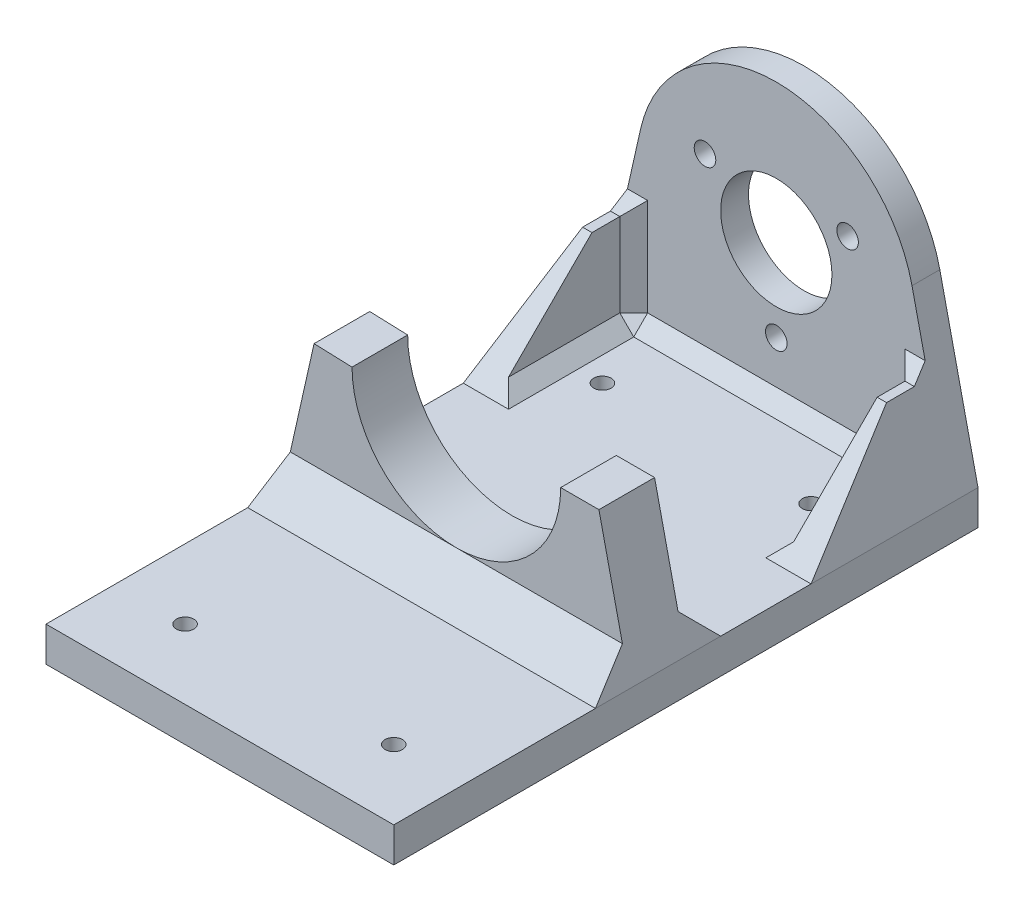
SolidWorks part; units mm, degrees
ref_plane "Plan de face" through (0, 0, 0) normal (0, 0, 1) x (1, 0, 0)
ref_plane "Plan de dessus" through (0, 0, 0) normal (0, 1, 0) x (1, 0, 0)
ref_plane "Plan de droite" through (0, 0, 0) normal (1, 0, 0) x (0, 0, -1)
sketch "Esquisse1" plane through (0, 0, 0) normal (0, 0, 1) x (1, 0, 0)
  line L0 (-25, -20) -> (-25, -25)
  line L1 (0, 0) -> (0, -30) construction
  line L2 (-25, -20) -> (-19.5122, 4.3902)
  line L3 (25, -20) -> (19.5122, 4.3902)
  line L4 (-25, -25) -> (25, -25)
  line L5 (25, -25) -> (25, -20)
  line L6 (0, -11.8357) -> (10.25, 5.9178) construction
  line L7 (10.25, 5.9178) -> (-10.25, 5.9178) construction
  line L8 (-10.25, 5.9178) -> (0, -11.8357) construction
  circle A0 centre (0, 0) radius 20 construction
  arc A1 (-19.5122, 4.3902) -> (19.5122, 4.3902) centre (0, 0) cw
  circle A2 centre (0, 0) radius 8
  circle A3 centre (0, 0) radius 5.9178 construction
  circle A4 centre (-10.25, 5.9178) radius 1.55
  circle A5 centre (10.25, 5.9178) radius 1.55
  circle A6 centre (0, -11.8357) radius 1.55
  point P20 (0, 0)
  point P24 (0, 0)
  dimension "D1" = 40
  dimension "D5" = 60
  dimension "D6" = 60
  dimension "D8" = 3.1
  dimension "D2" = 50
  dimension "D3" = 5
  dimension "D4" = 25
  dimension "D7" = 20.5
  dimension "D9" = 3
extrude "Boss.-Extru.1" add sketch "Esquisse1" along normal blind 4
sketch "Esquisse2" plane through (0, 0, 4) normal (0, 0, 1) x (1, 0, 0)
  line L0 (25, -25) -> (25, -20) construction
  line L1 (-25, -25) -> (25, -25)
  line L2 (-25, -25) -> (-25, -20)
  line L3 (-25, -20) -> (25, -20)
  line L4 (25, -25) -> (25, -20)
extrude "Boss.-Extru.2" add sketch "Esquisse2" along normal blind 80
sketch "Esquisse4" plane through (0, 0, 4) normal (0, 0, 1) x (1, 0, 0)
  line L0 (-20.5, 0) -> (-20.5, -20)
  line L1 (-19.5122, 4.3902) -> (-25, -20) construction
  line L2 (25, -20) -> (-25, -20) construction
  line L3 (-20.5, -20) -> (-25, -20)
  line L4 (-25, -20) -> (-25, -25) construction
  line L5 (-25, -20) -> (-20.5, 0)
  line L6 (0, 0) -> (0, -20) construction
  line L7 (25, -20) -> (-25, -20) construction
  line L8 (20.5, -20) -> (25, -20)
  line L9 (25, -20) -> (20.5, 0)
  line L10 (20.5, 0) -> (20.5, -20)
extrude "Boss.-Extru.3" add sketch "Esquisse4" along normal blind 20
sketch "Esquisse5" plane through (-20.5, 0, 0) normal (1, 0, 0) x (0, 0, -1)
  line L0 (-24, -20) -> (-4, 0) construction
  line L1 (-4, 0) -> (-24, 0)
  line L2 (-24, 0) -> (-24, -20)
  line L3 (-4, 0) -> (-4, -6)
  line L4 (-4, 0) -> (-4, 4.3902) construction
  line L5 (-4, -6) -> (-10, -6)
  line L6 (-10, -6) -> (-24, -20)
extrude "Enlèv. mat.-Extru.2" cut sketch "Esquisse5" against normal through all and the other way through all
chamfer "Chanfrein1" distance 2 angle 45 5 edges at (-20.5, -13, 4) (-20.5, -20, 14) (20.5, -13, 4) (20.5, -20, 14) (0, -20, 4)
chamfer "Chanfrein2" distance 2 angle 45 2 edges at (20.175, -6, 4) (-20.175, -6, 4)
ref_plane "Plan1" through (0, 0, 46) normal (0, 0, 1) x (1, 0, 0)
sketch "Esquisse7" plane through (0, 0, 46) normal (0, 0, 1) x (1, 0, 0)
  line L0 (-15, 0) -> (-20.4561, 0.1951)
  line L1 (-19.5122, 4.3902) -> (-21.4, -4) construction
  line L2 (-20.4561, 0.1951) -> (-25, -20)
  line L3 (-25, -20) -> (25, -20)
  line L4 (25, -20) -> (20.5, 0)
  line L5 (21.4, -4) -> (19.5122, 4.3902) construction
  line L6 (20.5, 0) -> (15, 0)
  arc A0 (-15, 0) -> (15, 0) centre (0, 0) ccw
  point P0 (0, 0)
extrude "Boss.-Extru.4" add sketch "Esquisse7" along normal blind 4 and the other way blind 4
chamfer "Chanfrein3" distance 5 angle 45 2 edges at (0, -20, 42) (0, -20, 50)
sketch "Esquisse6" plane through (0, -20, 0) normal (0, 1, 0) x (1, 0, 0)
  line L0 (0, 0) -> (0, -84) construction
  line L1 (25, -84) -> (-25, -84) construction
  line L2 (-25, -44) -> (25, -44) construction
  line L3 (-25, -84) -> (-25, -55) construction
  line L4 (25, -84) -> (25, -55) construction
  circle A0 centre (-15, -74) radius 1.25
  circle A1 centre (15, -74) radius 1.25
  circle A2 centre (15, -14) radius 1.25
  circle A3 centre (-15, -14) radius 1.25
  circle A4 centre (-15, -44) radius 1.25
  circle A5 centre (15, -44) radius 1.25
  dimension "D2" = 10
  dimension "D1" = 40
  dimension "D3" = 10
  dimension "D4" = 2
extrude "Enlèv. mat.-Extru.3" cut sketch "Esquisse6" against normal blind 20 and the other way blind 5
